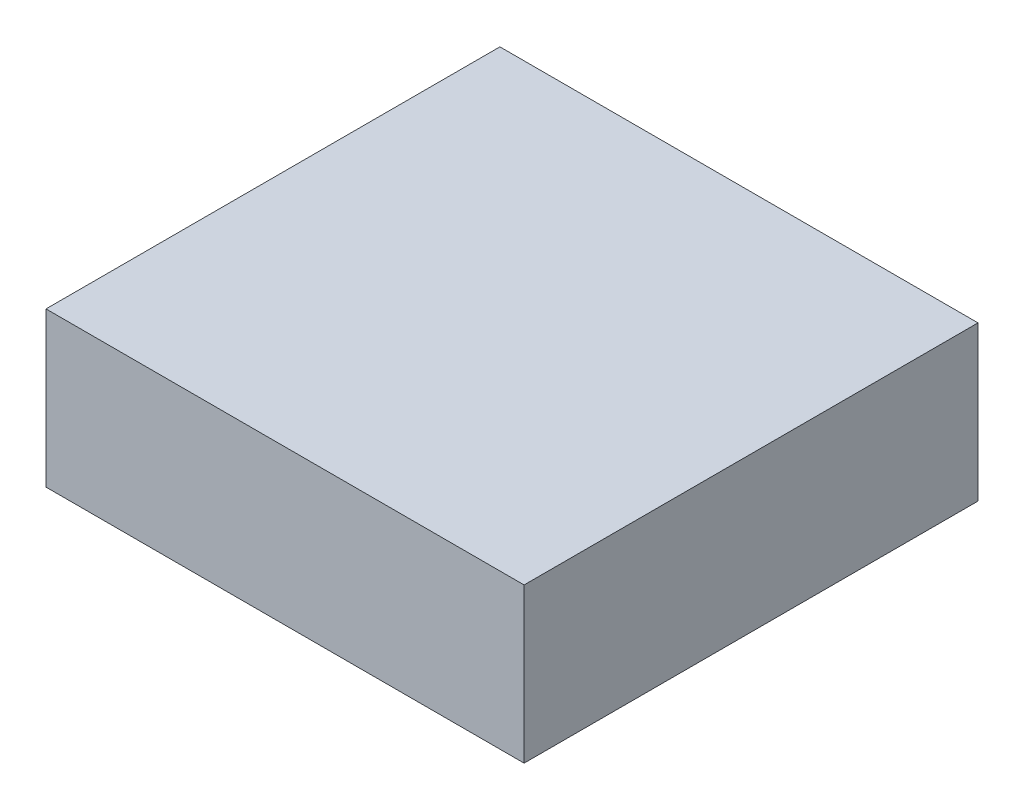
SolidWorks part; units mm, degrees
ref_plane "前视基准面" through (0, 0, 0) normal (0, 0, 1) x (1, 0, 0)
ref_plane "上视基准面" through (0, 0, 0) normal (0, 1, 0) x (1, 0, 0)
ref_plane "右视基准面" through (0, 0, 0) normal (1, 0, 0) x (0, 0, -1)
sketch "草图1" plane through (0, 0, 0) normal (0, 1, 0) x (1, 0, 0)
  line L0 (80, -50) -> (180, -50)
  line L1 (-50, -50) -> (50, -50)
  line L2 (-50, -50) -> (-50, 50)
  line L3 (-50, 50) -> (50, 50)
  line L4 (50, -50) -> (50, 50)
  line L5 (-50, -50) -> (50, 50) construction
  line L6 (-50, 50) -> (50, -50) construction
  line L7 (180, -50) -> (80, 50)
  line L8 (80, 50) -> (80, -50)
  point P0 (0, 0)
  dimension "D1" = 100
  dimension "D2" = 100
  dimension "D3" = 30
extrude "凸台-拉伸1" add sketch "草图1" along normal blind 30
ref_axis "基准轴1" through (0, 0, 0) along (0, 1, 0)
mirror "镜向1" about plane through (0, 0, 0) normal (1, 0, 0) of bodies 107
sketch "草图2" plane through (0, 0, 0) normal (0, -1, 0) x (1, 0, 0)
  line L0 (0, 0) -> (0.6563, -30) construction
  line L1 (-24.3437, -30) -> (25.6563, -30) construction
  line L2 (-24.3437, -22.5) -> (25.6563, -22.5)
  line L3 (-24.3437, -37.5) -> (25.6563, -37.5)
  circle A0 centre (0, 0) radius 7.5
  arc A1 (-24.3437, -22.5) -> (-24.3437, -37.5) centre (-24.3437, -30) ccw
  arc A2 (25.6563, -37.5) -> (25.6563, -22.5) centre (25.6563, -30) ccw
  point P7 (0.6563, -30)
  dimension "D1" = 15
  dimension "D2" = 15
  dimension "D3" = 50
  dimension "D4" = 30
extrude "切除-拉伸1" cut sketch "草图2" against normal blind 10
sketch "草图3" plane through (0, 0, 0) normal (0, -1, 0) x (1, 0, 0)
  line L0 (80, 50) -> (80, -50) construction
  line L1 (80, -50) -> (180, 50) construction
  line L2 (180, 50) -> (80, 50) construction
  line L3 (-80, -50) -> (-80, 50) construction
  line L4 (-80, 50) -> (-180, 50) construction
  line L5 (-180, 50) -> (-80, -50) construction
  line L6 (80, 50) -> (80, -50)
  line L7 (80, -50) -> (180, 50)
  line L8 (180, 50) -> (80, 50)
  line L9 (-80, -50) -> (-80, 50)
  line L10 (-80, 50) -> (-180, 50)
  line L11 (-180, 50) -> (-80, -50)
extrude "切除-拉伸2" cut sketch "草图3" against normal through all
sketch "草图4" plane through (0, 0, 0) normal (0, -1, 0) x (1, 0, 0)
  line L0 (50, 50) -> (50, -50) construction
  line L1 (-50, 50) -> (50, 50)
  line L2 (-50, 50) -> (-50, 38.2204)
  line L3 (-50, 38.2204) -> (50, 38.2204)
  line L4 (50, 50) -> (50, 38.2204)
extrude "切除-拉伸3" cut sketch "草图4" against normal through all
sketch "草图5" plane through (0, 0, 0) normal (0, -1, 0) x (1, 0, 0)
  line L0 (50, -50) -> (-50, -50) construction
  line L1 (-50, 38.2204) -> (-42.9248, 38.2204)
  line L2 (-50, 38.2204) -> (-50, -50)
  line L3 (-50, -50) -> (-42.9248, -50)
  line L4 (-42.9248, 38.2204) -> (-42.9248, -50)
extrude "切除-拉伸5" cut sketch "草图5" against normal through all
